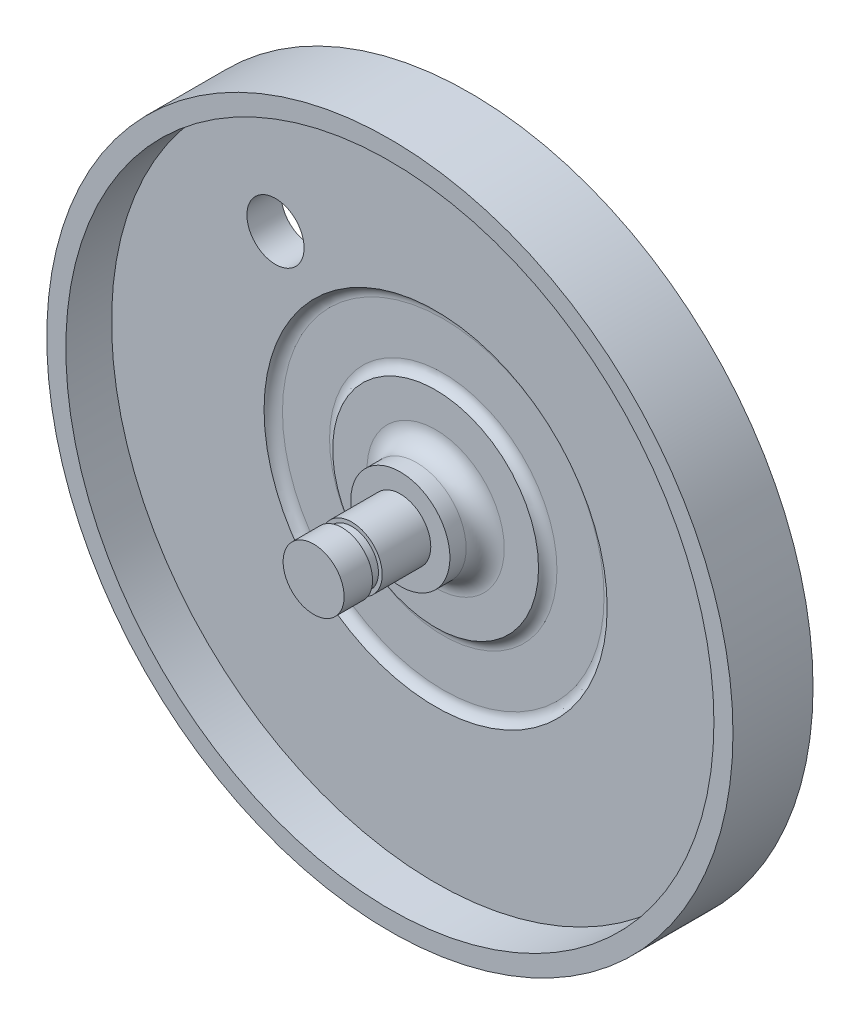
SolidWorks part; units mm, degrees
ref_plane "Front Plane" through (0, 0, 0) normal (0, 0, 1) x (1, 0, 0)
ref_plane "Top Plane" through (0, 0, 0) normal (0, 1, 0) x (1, 0, 0)
ref_plane "Right Plane" through (0, 0, 0) normal (1, 0, 0) x (0, 0, -1)
sketch "Sketch1" plane through (0, 0, 0) normal (0, 0, 1) x (1, 0, 0)
  circle A0 centre (0, 0) radius 45
  dimension "D1" = 90
extrude "Boss-Extrude1" add sketch "Sketch1" along normal blind 2.5 and the other way blind 2 contours A0
sketch "Sketch2" plane through (0, 0, 2.5) normal (0, 0, 1) x (1, 0, 0)
  circle A0 centre (0, 0) radius 42.5
  circle A1 centre (0, 0) radius 45
  dimension "D1" = 85
  dimension "D2" = 90
extrude "Boss-Extrude2" add sketch "Sketch2" along normal blind 6 contours A0 | A1
sketch "Sketch3" plane through (0, 0, 2.5) normal (0, 0, 1) x (1, 0, 0)
  circle A0 centre (0, 0) radius 4
  dimension "D1" = 8
extrude "Boss-Extrude3" add sketch "Sketch3" along normal blind 16 contours A0
ref_plane "Plane1" through (0, 0, 13.5) normal (0, 0, 1) x (1, 0, 0)
sketch "Sketch4" plane through (0, 0, 13.5) normal (0, 0, 1) x (1, 0, 0)
  circle A0 centre (0, 0) radius 4
  circle A1 centre (0, 0) radius 3.5
  dimension "D1" = 8
  dimension "D2" = 7
extrude "Cut-Extrude1" cut sketch "Sketch4" along normal blind 1.27
ref_plane "Plane2" through (0, 0, 7.135) normal (0, 0, 1) x (1, 0, 0)
sketch "Sketch5" plane through (0, 0, 7.135) normal (0, 0, 1) x (1, 0, 0)
  circle A0 centre (0, 0) radius 4
  circle A1 centre (0, 0) radius 3.5
  dimension "D1" = 8
  dimension "D2" = 7
extrude "Cut-Extrude2" cut sketch "Sketch5" against normal blind 1.27 contours A0 | A1
sketch "Sketch6" plane through (0, 0, -2) normal (0, 0, -1) x (-1, 0, 0)
  line L1 (-6.6395, 0) -> (-3.3198, -5.75)
  line L2 (-3.3198, -5.75) -> (3.3198, -5.75)
  line L3 (3.3198, -5.75) -> (6.6395, 0)
  line L4 (6.6395, 0) -> (3.3198, 5.75)
  line L5 (3.3198, 5.75) -> (-3.3198, 5.75)
  line L6 (-3.3198, 5.75) -> (-6.6395, 0)
  circle A0 centre (0, 0) radius 5.75 construction
  dimension "D1" = 11.5
extrude "Cut-Extrude3" cut sketch "Sketch6" against normal blind 2 contours L5 L6 L1 L2 L3 L4
sketch "Sketch7" plane through (0, 0, 2.5) normal (0, 0, 1) x (1, 0, 0)
  circle A0 centre (-21, 21) radius 3.75
  dimension "D1" = 7.5
  dimension "D2" = 21
  dimension "D3" = 21
extrude "Cut-Extrude4" cut sketch "Sketch7" against normal through all
sketch "Sketch8" plane through (0, 0, 2.5) normal (0, 0, 1) x (1, 0, 0)
  circle A0 centre (0, 0) radius 13.5
  circle A1 centre (0, 0) radius 22.5
  dimension "D1" = 45
  dimension "D2" = 27
extrude "Cut-Extrude5" cut sketch "Sketch8" against normal blind 1 contours A1 | A0
fillet "Fillet2" radius 1.5 2 edges at (13.5, 0, 1.5) (22.5, 0, 1.5)
sketch "Sketch11" plane through (0, 0, 0) normal (0, 0, -1) x (-1, 0, 0)
  circle A0 centre (0, 0) radius 6.5
  dimension "D1" = 13
extrude "Boss-Extrude4" add sketch "Sketch11" against normal blind 7.127
fillet "Fillet3" radius 2.5 1 edges at (6.5, 0, 2.5)
